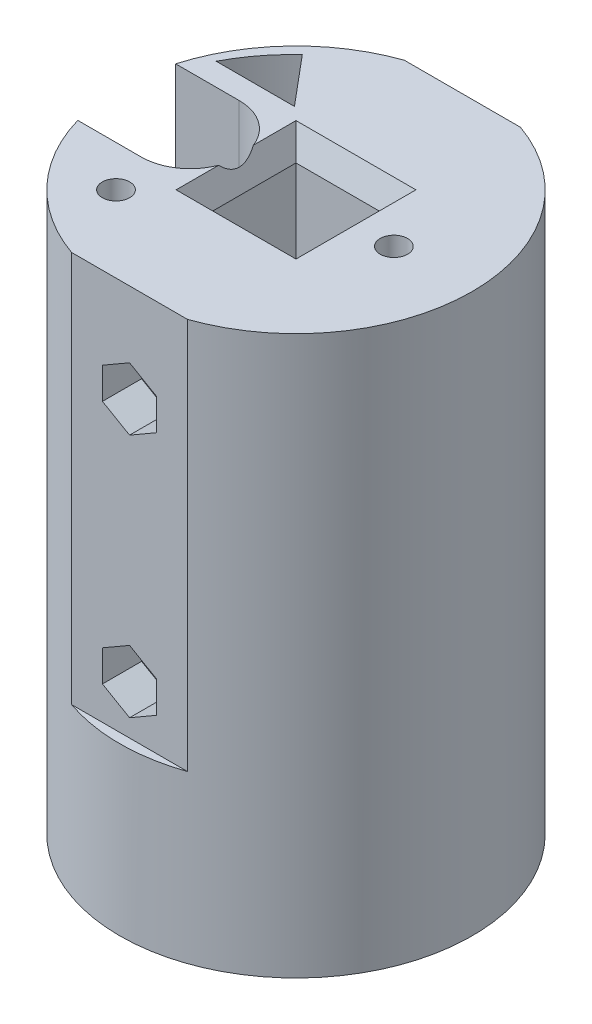
SolidWorks part; units mm, degrees
ref_plane "Спереди" through (0, 0, 0) normal (0, 0, 1) x (1, 0, 0)
ref_plane "Сверху" through (0, 0, 0) normal (0, 1, 0) x (1, 0, 0)
ref_plane "Справа" through (0, 0, 0) normal (1, 0, 0) x (0, 0, -1)
sketch "Sketch1" plane through (0, 0, 0) normal (0, 1, 0) x (1, 0, 0)
  line L0 (-5.125, 0) -> (-18, 0) construction
  line L1 (5.125, -5.125) -> (-5.125, -5.125)
  line L2 (5.125, -5.125) -> (5.125, 5.125)
  line L3 (5.125, 5.125) -> (-5.125, 5.125)
  line L4 (-5.125, -5.125) -> (-5.125, 5.125)
  line L5 (5.125, -5.125) -> (-5.125, 5.125) construction
  line L6 (5.125, 5.125) -> (-5.125, -5.125) construction
  circle A0 centre (0, 0) radius 18
  circle A1 centre (-12, 0) radius 2
  dimension "D1" = 36
  dimension "D3" = 6
  dimension "D2" = 10.25
extrude "Boss-Extrude1" add sketch "Sketch1" along normal blind 57
sketch "Sketch2" plane through (0, 57, 0) normal (0, 1, 0) x (1, 0, 0)
  line L0 (-10.8, 5) -> (-17.2916, 5)
  line L1 (-10.8, -5) -> (-17.2916, -5)
  line L2 (-5.125, 0) -> (-18, 0) construction
  line L3 (-5.125, 5.125) -> (-5.125, -5.125) construction
  circle A1 centre (0, 0) radius 18 construction
  arc A2 (-17.2916, 5) -> (-17.2916, -5) centre (0, 0) ccw
  arc A3 (-10.8, 5) -> (-10.8, -5) centre (-10.8, 0) cw
  point P12 (-5.8, 0)
  dimension "D1" = 5
extrude "Cut-Extrude1" cut sketch "Sketch2" against normal blind 25
sketch "Sketch4" plane through (0, 0, 0) normal (0, -1, 0) x (-1, 0, 0)
  line L0 (0, 0) -> (18, 21.4516) construction
  line L1 (0, 0) -> (18, -21.4516) construction
  line L2 (18, 21.4516) -> (18, -21.4516) construction
  line L3 (0, 0) -> (13.6996, 11.6756) construction
  line L4 (0, 0) -> (13.6996, -11.6756) construction
  line L5 (0, 0) -> (18, 0) construction
  line L6 (5.125, 5.125) -> (5.125, -5.125) construction
  line L7 (11.5702, 13.7888) -> (5.1423, 6.1284) construction
  line L8 (5.1423, 6.1284) -> (5.1423, -4.3826) construction
  line L9 (5.1423, -4.3826) -> (13.6996, -11.6756) construction
  line L10 (5.1423, 0.8729) -> (18.1354, 0.8729) construction
  line L12 (15.8104, 5.5479) -> (6.4604, 5.5479)
  line L13 (15.8104, 5.5479) -> (15.8104, -3.8021)
  line L14 (15.8104, -3.8021) -> (6.4604, -3.8021)
  line L15 (6.4604, 5.5479) -> (6.4604, -3.8021)
  line L16 (15.8104, 5.5479) -> (6.4604, -3.8021) construction
  line L17 (15.8104, -3.8021) -> (6.4604, 5.5479) construction
  arc A0 (13.6996, -11.6756) -> (11.5702, 13.7888) centre (0.5154, 0.0431) ccw construction
  circle A2 centre (0, 0) radius 18 construction
  point P2 (11, 0)
  point P5 (11.5702, 13.7888)
  point P7 (4.1157, 3.5076)
  point P8 (11.5702, -13.7888)
  point P11 (5.125, -6.1077)
  point P16 (11.1354, 0.8729)
  dimension "D5" = 10
  dimension "D1" = 100
  dimension "D2" = 3
  dimension "D3" = 3
  dimension "D4" = 9.35
  dimension "D6" = 7
extrude "Cut-Extrude3" cut sketch "Sketch4" against normal blind 20.4
sketch "Sketch5" plane through (0, 57, 0) normal (0, 1, 0) x (1, 0, 0)
  line L0 (0, 18) -> (0, -18) construction
  line L1 (5.9161, 17) -> (-5.9161, 17)
  line L2 (5.9161, -17) -> (-5.9161, -17)
  circle A0 centre (0, 0) radius 18 construction
  arc A1 (5.9161, 17) -> (-5.9161, 17) centre (0, 0) ccw
  arc A2 (5.9161, -17) -> (-5.9161, -17) centre (0, 0) cw
  point P11 (0, 17)
  dimension "D1" = 1
extrude "Cut-Extrude4" cut sketch "Sketch5" against normal blind 40
sketch "Sketch6" plane through (0, 0, -17) normal (0, 0, -1) x (-1, 0, 0)
  line L0 (0, 57) -> (0, 0) construction
  line L1 (5.9161, 57) -> (-5.9161, 57) construction
  line L2 (5.9161, 17) -> (-5.9161, 17) construction
  line L3 (5.9161, 0) -> (-5.9161, 0) construction
  circle A0 centre (0, 47) radius 1.5
  circle A1 centre (0, 22) radius 1.5
  dimension "D1" = 3
  dimension "D2" = 10
  dimension "D3" = 5
extrude "Cut-Extrude5" cut sketch "Sketch6" against normal through all
sketch "Sketch7" plane through (0, 0, -17) normal (0, 0, -1) x (-1, 0, 0)
  circle A0 centre (0, 47) radius 3
  circle A1 centre (0, 22) radius 3
  dimension "D1" = 6
extrude "Cut-Extrude6" cut sketch "Sketch7" against normal blind 3
sketch "Sketch8" plane through (0, 0, 17) normal (0, 0, 1) x (1, 0, 0)
  line L0 (5.9161, 17) -> (5.9161, 57) construction
  line L1 (0, 43.8) -> (2.7713, 45.4)
  line L2 (2.7713, 45.4) -> (2.7713, 48.6)
  line L3 (2.7713, 48.6) -> (0, 50.2)
  line L4 (0, 50.2) -> (-2.7713, 48.6)
  line L5 (-2.7713, 48.6) -> (-2.7713, 45.4)
  line L6 (-2.7713, 45.4) -> (0, 43.8)
  line L9 (0, 18.8) -> (2.7713, 20.4)
  line L10 (2.7713, 20.4) -> (2.7713, 23.6)
  line L11 (2.7713, 23.6) -> (0, 25.2)
  line L12 (0, 25.2) -> (-2.7713, 23.6)
  line L13 (-2.7713, 23.6) -> (-2.7713, 20.4)
  line L14 (-2.7713, 20.4) -> (0, 18.8)
  circle A0 centre (0, 47) radius 3.2 construction
  circle A1 centre (0, 22) radius 3.2 construction
  dimension "D1" = 6.4
extrude "Cut-Extrude7" cut sketch "Sketch8" against normal blind 4
chamfer "Chamfer1" distance 1 angle 70 4 edges at (-5.125, 57, 0) (0, 57, -5.125) (0, 57, 5.125) (5.125, 57, 0) first distance on face at (-5.2523, 57, 0)
sketch "Sketch9" plane through (0, 0, 0) normal (0, -1, 0) x (1, 0, 0)
  line L0 (16.4542, -7.2979) -> (-16.4542, -7.2979) construction
  line L1 (-15.8104, -5.5479) -> (-6.4604, -5.5479) construction
  line L2 (-7.4542, -7.2979) -> (-15.4542, -7.2979)
  line L3 (-7.4542, -7.2979) -> (-11.6323, -12.2772)
  line L4 (5.125, -5.125) -> (-5.125, -5.125) construction
  circle A0 centre (0, 0) radius 18 construction
  arc A1 (-15.4542, -7.2979) -> (-11.6323, -12.2772) centre (0.5168, 1.0043) ccw
  point P10 (-11.4542, -7.2979)
  dimension "D8" = 18
  dimension "D1" = 1.75
  dimension "D2" = 5
  dimension "D3" = 6.5
  dimension "D4" = 50
  dimension "D5" = 8
  dimension "D6" = 2.1729
  dimension "D7" = 23.9084
extrude "Cut-Extrude8" cut sketch "Sketch9" against normal through all
sketch "Sketch12" plane through (0, 57, 0) normal (0, 1, 0) x (1, 0, 0)
  line L0 (18, 0) -> (-10.8, 0) construction
  line L1 (0, 0) -> (-12.7279, -12.7279) construction
  arc A0 (5.9161, -17) -> (5.9161, 17) centre (0, 0) ccw construction
  arc A1 (-17.2916, -5) -> (-5.9161, -17) centre (0, 0) ccw construction
  circle A2 centre (10, 0) radius 1.4
  circle A3 centre (-9.1924, -9.1924) radius 1.4
  dimension "D1" = 2.8
  dimension "D2" = 10
  dimension "D3" = 13
extrude "Cut-Extrude10" cut sketch "Sketch12" against normal blind 20
